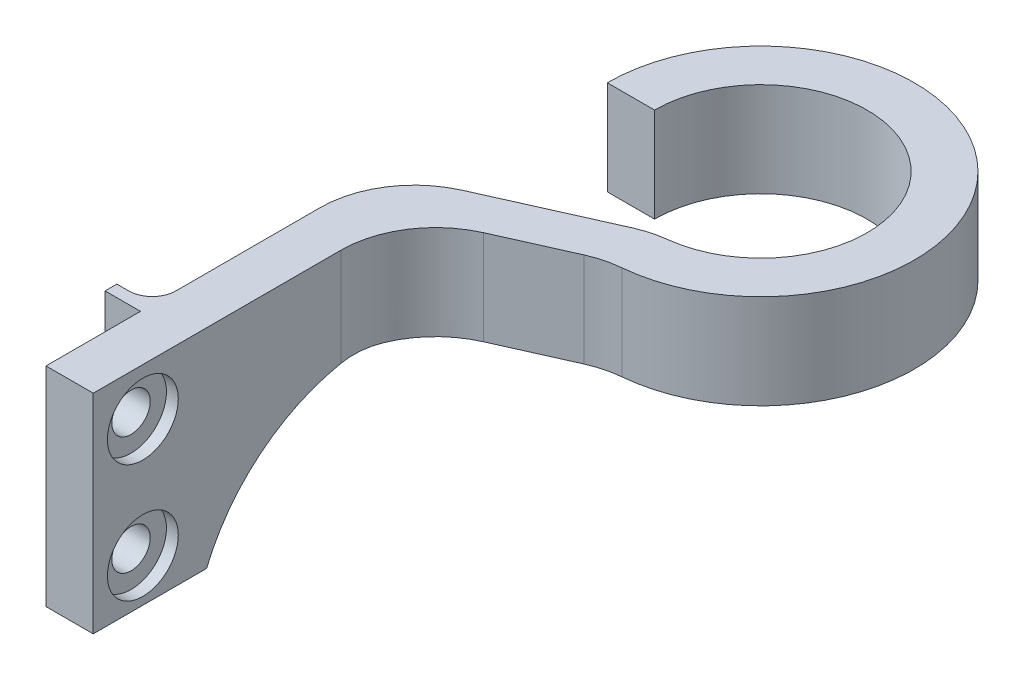
SolidWorks part; units mm, degrees
ref_plane "Front Plane" through (0, 0, 0) normal (0, 0, 1) x (1, 0, 0)
ref_plane "Top Plane" through (0, 0, 0) normal (0, 1, 0) x (1, 0, 0)
ref_plane "Right Plane" through (0, 0, 0) normal (1, 0, 0) x (0, 0, -1)
sketch "Sketch1" plane through (0, 0, 0) normal (0, 1, 0) x (1, 0, 0)
  line L1 (-16, -16.1332) -> (-16, -44.5201)
  line L2 (-16, -44.5201) -> (-12, -44.5201)
  line L3 (-9, 0) -> (-13, 0)
  line L4 (-12, -44.5201) -> (-12, -18.3499)
  line L5 (-12, -18.3499) -> (0, -13)
  line L6 (-16, -16.1332) -> (0, -9)
  arc A0 (0, -9) -> (-9, 0) centre (0, 0) ccw
  arc A1 (0, -13) -> (-13, 0) centre (0, 0) ccw
  dimension "D1" = 18
  dimension "D2" = 4
  dimension "D4" = 4
extrude "Boss-Extrude1" add sketch "Sketch1" along normal blind 8
sketch "Sketch2" plane through (-16, 0, 0) normal (-1, 0, 0) x (0, 0, 1)
  line L0 (44.5201, 0) -> (44.5201, -9.6498)
  line L1 (44.5201, 0) -> (18.3499, 0) construction
  line L2 (44.5201, -9.6498) -> (34.927, -9.6498)
  line L3 (44.5201, 0) -> (20.5201, 0)
  line L4 (44.5201, 8) -> (44.5201, 0) construction
  line L5 (16.1332, 0) -> (44.5201, 0) construction
  arc A0 (34.927, -9.6498) -> (20.5201, 0) centre (20.5201, -15.5794) ccw
extrude "Boss-Extrude2" add sketch "Sketch2" against normal blind 4
fillet "Fillet1" radius 8 4 edges at (0, 4, 9) (0, 4, 13) (-16, 4, 16.1332) (-12, 4, 18.3499)
sketch "Sketch3" plane through (-12, 0, 0) normal (1, 0, 0) x (0, 0, -1)
  circle A0 centre (-40.3201, 4) radius 1.625
  circle A1 centre (-40.3201, -6) radius 1.625
  dimension "D1" = 3.25
extrude "Cut-Extrude1" cut sketch "Sketch3" against normal through all
sketch "Sketch4" plane through (-12, 0, 0) normal (1, 0, 0) x (0, 0, -1)
  circle A0 centre (-40.3201, 4) radius 3
  circle A1 centre (-40.3201, -6) radius 3
  dimension "D2" = 6
extrude "Cut-Extrude2" cut sketch "Sketch4" against normal blind 1
sketch "Sketch5" plane through (-16, 0, 0) normal (-1, 0, 0) x (0, 0, 1)
  line L0 (21.3256, 8) -> (44.5201, 8) construction
  line L1 (36.5201, 8) -> (35.5201, 8)
  line L2 (36.5201, 8) -> (36.5201, -9.6498)
  line L3 (36.5201, -9.6498) -> (35.5201, -9.6498)
  line L4 (35.5201, 8) -> (35.5201, -9.6498)
  line L6 (34.927, -9.6498) -> (44.5201, -9.6498) construction
  dimension "D1" = 1
extrude "Boss-Extrude3" add sketch "Sketch5" along normal blind 3
fillet "Fillet2" radius 2 1 edges at (-16, -0.8249, 35.5201)
